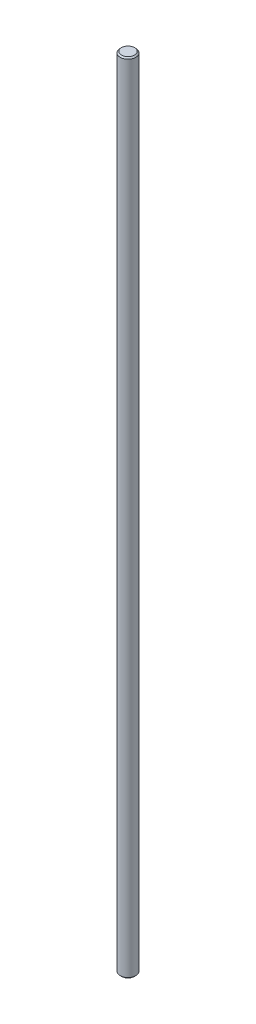
SolidWorks part; units mm, degrees
ref_plane "Front Plane" through (0, 0, 0) normal (0, 0, 1) x (1, 0, 0)
ref_plane "Top Plane" through (0, 0, 0) normal (0, 1, 0) x (1, 0, 0)
ref_plane "Right Plane" through (0, 0, 0) normal (1, 0, 0) x (0, 0, -1)
sketch "Sketch1" plane through (0, 0, 0) normal (0, 1, 0) x (1, 0, 0)
  circle A0 centre (0, 0) radius 3
  dimension "D1" = 6
extrude "Boss-Extrude1" add sketch "Sketch1" along normal blind 306
chamfer "Chamfer1" distance 0.5 angle 45 1 edges at (0, 0, 3)
chamfer "Chamfer2" distance 0.5 angle 45 1 edges at (0, 306, 3)
sketch "Sketch2" plane through (0, 0, 0) normal (0, -1, 0) x (1, 0, 0)
  circle A0 centre (0, 0) radius 3 construction
  circle A1 centre (0, 0) radius 3
curve "Helix/Spiral1" [suppressed] pitch 0.7 height 155 turns 221.4286
sketch "Sketch3" [suppressed] plane through (0, 0, 0) normal (1, 0, 0) x (0, 0, -1)
  line L0 (2, 0) -> (1.4696, 0) construction
  line L1 (1.6211, -0.0875) -> (2.2652, -0.4594)
  line L2 (2.2652, -0.4594) -> (2.2652, 0.4594)
  line L3 (2.2652, 0.4594) -> (1.6211, 0.0875)
  line L4 (-1.5, 0) -> (1.5, 0) construction
  circle A0 centre (2, 0) radius 0.2652 construction
  arc A1 (1.6211, 0.0875) -> (1.6211, -0.0875) centre (1.6716, 0) ccw
  point P7 (1.6211, 0)
  dimension "D1" = 0.5304
  dimension "D2" = 0.1515
sweep "Cut-Sweep1" [suppressed] cut profiles "Sketch3" path "Helix/Spiral1"
